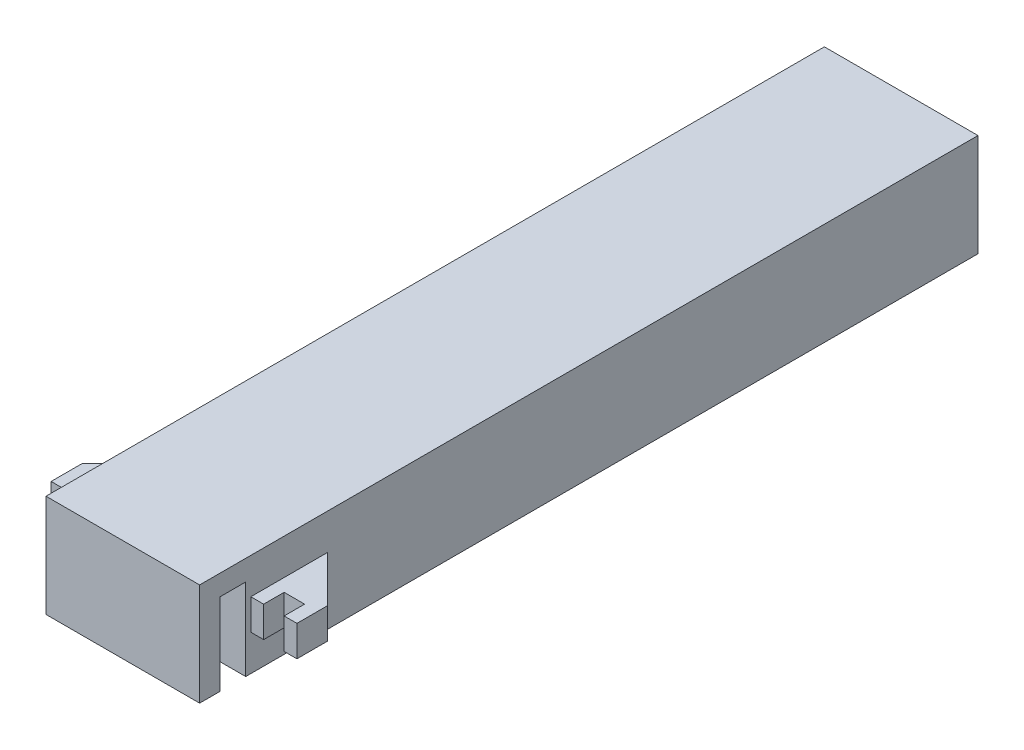
SolidWorks part; units mm, degrees
ref_plane "Front Plane" through (0, 0, 0) normal (0, 0, 1) x (1, 0, 0)
ref_plane "Top Plane" through (0, 0, 0) normal (0, 1, 0) x (1, 0, 0)
ref_plane "Right Plane" through (0, 0, 0) normal (1, 0, 0) x (0, 0, -1)
sketch "Sketch1" plane through (0, 0, 0) normal (0, 1, 0) x (1, 0, 0)
  line L1 (-7.5, 38) -> (7.5, 38)
  line L2 (-7.5, 38) -> (-7.5, -38)
  line L3 (-7.5, -38) -> (7.5, -38)
  line L4 (7.5, 38) -> (7.5, -38)
  line L5 (-7.5, 38) -> (7.5, -38) construction
  line L6 (-7.5, -38) -> (7.5, 38) construction
  point P0 (0, 0)
  dimension "D1" = 76
  dimension "D2" = 15
extrude "Boss-Extrude1" add sketch "Sketch1" along normal blind 10
ref_plane "Plane1" through (0, 0, 0) normal (-1, 0, 0) x (0, 0, 1)
sketch "Sketch3" plane through (0, 0, 0) normal (-1, 0, 0) x (0, 0, 1)
  line L0 (-38, 5) -> (27, 5)
  line L1 (-38, 10) -> (-38, 0) construction
  line L2 (38, 10) -> (38, 0) construction
  line L4 (31, 1) -> (31, 0)
  line L5 (-38, 0) -> (38, 0) construction
  arc A1 (31, 1) -> (27, 5) centre (27, 1) ccw
  point P1 (0, 0)
  point P9 (31, 5)
  point P13 (0, 0)
  point P14 (0, 0)
  point P15 (0, 0)
  dimension "D1" = 4
  dimension "D2" = 7
sketch "Sketch4" plane through (0, 0, -38) normal (0, 0, -1) x (-1, 0, 0)
  line L1 (0, -55.5125) -> (0, 55.5125) construction
  line L2 (-7.5, 10) -> (-7.5, 0) construction
  circle A0 centre (0, 5) radius 2.5
  point P6 (0, 0)
  point P9 (-7.5, 5)
  point P10 (0, 0)
  dimension "D1" = 5
sweep "Cut-Sweep2" cut profiles "Sketch4" path "Sketch3"
sketch "Sketch5" plane through (-7.5, 0, 0) normal (-1, 0, 0) x (0, 0, 1)
  line L0 (38, 10) -> (38, 0) construction
  line L1 (30, 6.5) -> (33, 6.5)
  line L2 (30, 6.5) -> (30, 3.5)
  line L3 (30, 3.5) -> (33, 3.5)
  line L4 (33, 6.5) -> (33, 3.5)
  line L5 (30, 6.5) -> (33, 3.5) construction
  line L6 (30, 3.5) -> (33, 6.5) construction
  point P0 (31.5, 5)
  point P7 (38, 5)
  point P8 (33, 5)
  dimension "D1" = 3
  dimension "D2" = 5
extrude "Boss-Extrude2" add sketch "Sketch5" along normal blind 4.5
ref_plane "Plane2" through (0, 0, 0) normal (-1, 0, 0) x (0, 0, 1)
mirror "Mirror1" about plane through (0, 0, 0) normal (-1, 0, 0) of "Boss-Extrude2"
sketch "Sketch6" plane through (0, 0, 33) normal (0, 0, 1) x (1, 0, 0)
  line L0 (-12, 6.5) -> (-7.5, 6.5) construction
  line L1 (-10.75, 6.5) -> (-8.75, 6.5)
  line L2 (-10.75, 6.5) -> (-10.75, 3.5)
  line L3 (-10.75, 3.5) -> (-8.75, 3.5)
  line L4 (-8.75, 6.5) -> (-8.75, 3.5)
  line L5 (-10.75, 6.5) -> (-8.75, 3.5) construction
  line L6 (-10.75, 3.5) -> (-8.75, 6.5) construction
  line L7 (-12, 3.5) -> (-7.5, 3.5) construction
  point P0 (-9.75, 5)
  point P7 (-9.75, 6.5)
  point P8 (-9.75, 6.5)
  dimension "D2" = 2
extrude "Cut-Extrude2" cut sketch "Sketch6" against normal offset from surface (2 mm away) 1 up to face at (-9.75, 5, 30)
mirror "Mirror2" about plane through (0, 0, 0) normal (-1, 0, 0) of "Cut-Extrude2"
sketch "Sketch7" plane through (0, 6.5, 0) normal (0, 1, 0) x (1, 0, 0)
  line L0 (-12, -30) -> (-7.5, -25.5)
  line L1 (-7.5, 38) -> (-7.5, -38) construction
  line L2 (-7.5, -25.5) -> (-7.5, -30)
  line L3 (-7.5, -30) -> (-12, -30)
extrude "Boss-Extrude3" add sketch "Sketch7" against normal up to surface (3 mm away) up to face at (-9.75, 3.5, 31.75)
mirror "Mirror3" about plane through (0, 0, 0) normal (-1, 0, 0) of "Boss-Extrude3"
sketch "Sketch8" plane through (0, 0, 0) normal (0, -1, 0) x (1, 0, 0)
  line L0 (-7.5, -38) -> (-7.5, 38) construction
  line L1 (-4.5, 36) -> (-7.5, 36)
  line L2 (-4.5, 36) -> (-4.5, 33.5)
  line L3 (-4.5, 33.5) -> (-7.5, 33.5)
  line L4 (-7.5, 36) -> (-7.5, 33.5)
  line L5 (-4.5, 36) -> (-7.5, 33.5) construction
  line L6 (-4.5, 33.5) -> (-7.5, 36) construction
  line L7 (-7.5, 38) -> (7.5, 38) construction
  line L8 (0, 38) -> (0, -38) construction
  line L9 (7.5, -38) -> (-7.5, -38) construction
  line L10 (4.5, 33.5) -> (7.5, 36) construction
  line L11 (4.5, 36) -> (7.5, 33.5) construction
  line L12 (7.5, 36) -> (7.5, 33.5)
  line L13 (4.5, 33.5) -> (7.5, 33.5)
  line L14 (4.5, 36) -> (4.5, 33.5)
  line L15 (4.5, 36) -> (7.5, 36)
  point P0 (-6, 34.75)
  point P17 (6, 34.75)
  dimension "D1" = 2.5
  dimension "D2" = 3
  dimension "D3" = 2
extrude "Cut-Extrude3" cut sketch "Sketch8" against normal offset from surface (8 mm away) 2 up to face at (0, 10, 0)
